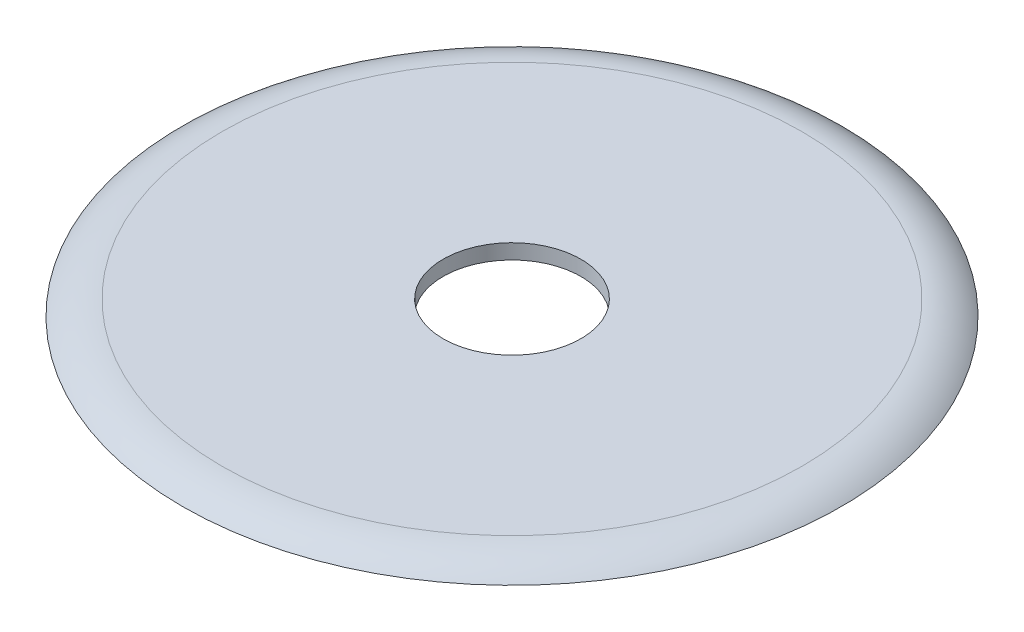
SolidWorks part; units mm, degrees
ref_plane "Front Plane" through (0, 0, 0) normal (0, 0, 1) x (1, 0, 0)
ref_plane "Top Plane" through (0, 0, 0) normal (0, 1, 0) x (1, 0, 0)
ref_plane "Right Plane" through (0, 0, 0) normal (1, 0, 0) x (0, 0, -1)
sketch "Sketch1" plane through (0, 0, 0) normal (0, 1, 0) x (1, 0, 0)
  circle A0 centre (0, 0) radius 55
  circle A1 centre (0, 0) radius 11.5
  dimension "D1" = 110
  dimension "D2" = 23
extrude "Boss-Extrude1" add sketch "Sketch1" along normal blind 2.5
fillet "Fillet1" radius 10 1 edges at (0, 2.5, 55)
